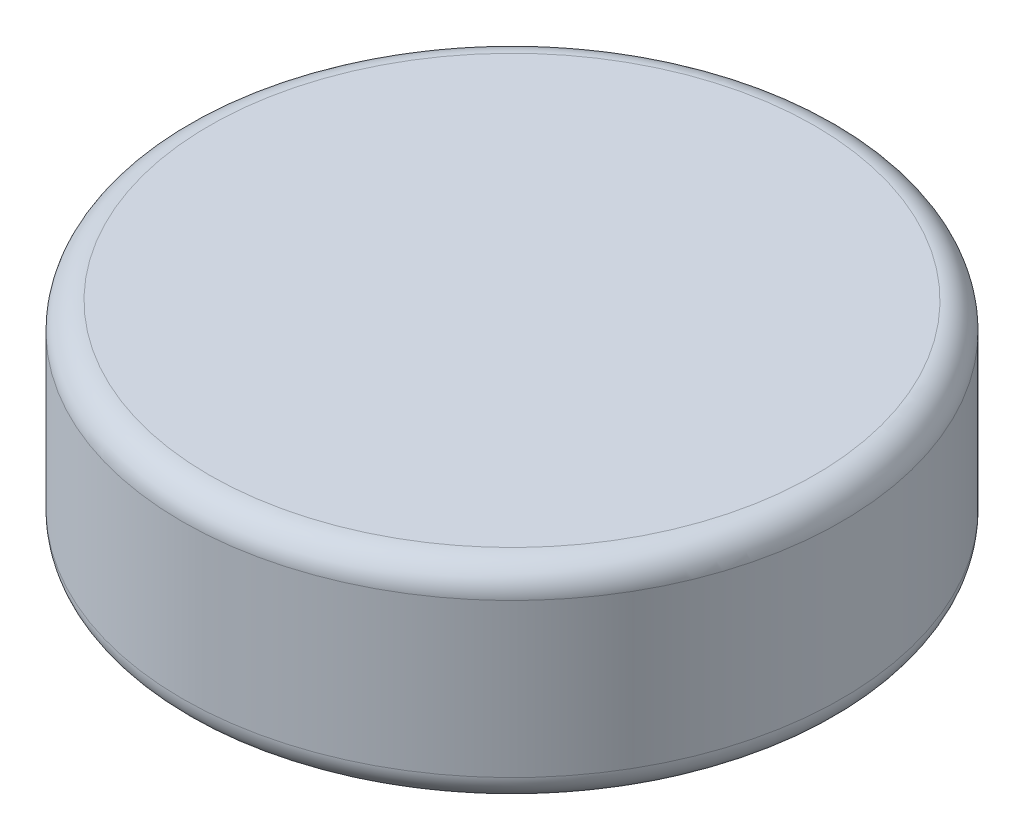
SolidWorks part; units mm, degrees
material "Plain Carbon Steel"
ref_plane "Front" through (0, 0, 0) normal (0, 0, 1) x (1, 0, 0)
ref_plane "Top" through (0, 0, 0) normal (0, 1, 0) x (1, 0, 0)
ref_plane "Right" through (0, 0, 0) normal (1, 0, 0) x (0, 0, -1)
sketch "Sketch1" plane through (0, 0, 0) normal (0, 1, 0) x (1, 0, 0)
  circle A0 centre (0, 0) radius 12.25
  dimension "D1" = 24.5
extrude "Boss-Extrude1" add sketch "Sketch1" along normal blind 7.7
fillet "Fillet1" radius 1 2 edges at (0, 0, 12.25) (0, 7.7, 12.25)
ref_axis "Axis1" [suppressed] through (-80.9, 0, 0) along (1, 0, 0)
pattern_linear "LPattern1" [suppressed] count 4 spacing 26 along (1, 0, 0) of bodies 101
